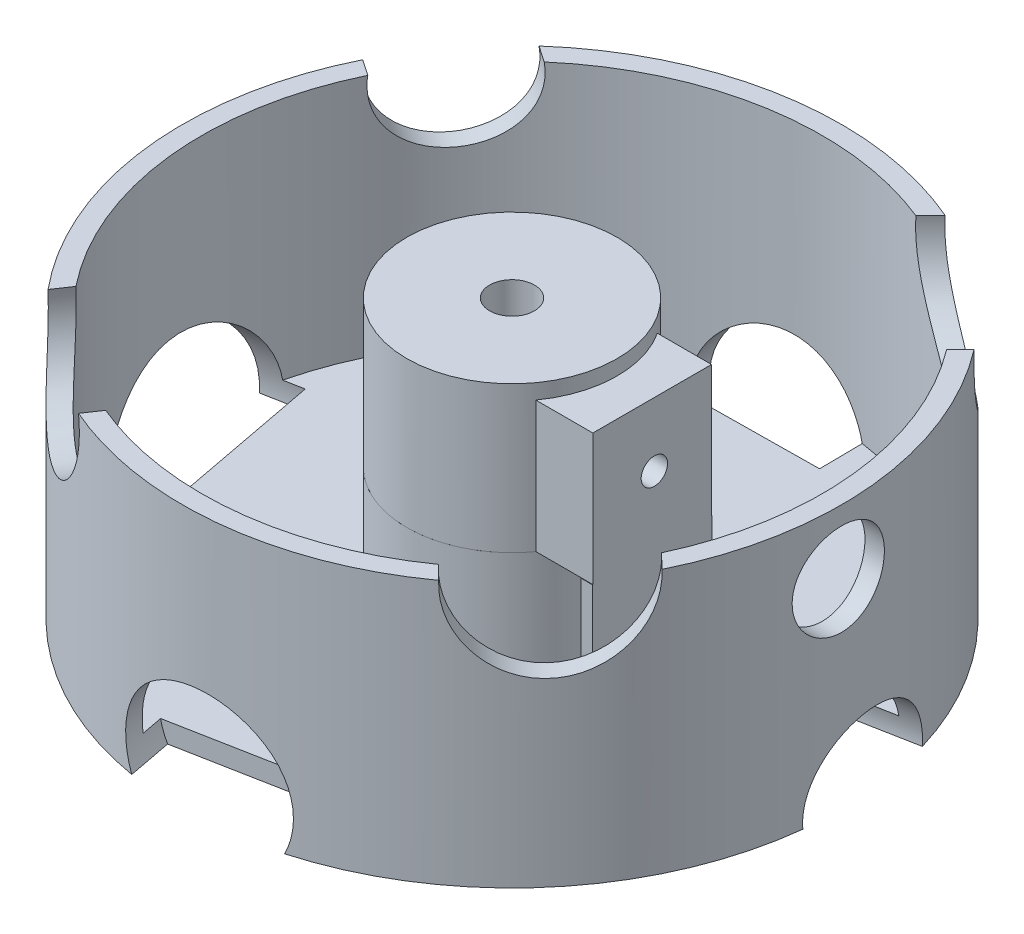
SolidWorks part; units mm, degrees
ref_plane "Front Plane" through (0, 0, 0) normal (0, 0, 1) x (1, 0, 0)
ref_plane "Top Plane" through (0, 0, 0) normal (0, 1, 0) x (1, 0, 0)
ref_plane "Right Plane" through (0, 0, 0) normal (1, 0, 0) x (0, 0, -1)
sketch "Sketch1" plane through (0, 0, 0) normal (0, 1, 0) x (1, 0, 0)
  circle A0 centre (0, 0) radius 15.958
extrude "ShaftHolderNearMotor" add sketch "Sketch1" along normal blind 22.19
sketch "Sketch2" plane through (0, 22.19, 0) normal (0, 1, 0) x (1, 0, 0)
  circle A0 centre (0, 0) radius 3.4
extrude "Cut-Extrude1" cut sketch "Sketch2" against normal blind 14.35 contours A0
ref_plane "Plane1" through (0, 19.65, 0) normal (0, 1, 0) x (1, 0, 0)
ref_axis "Axis1" through (0, 7.84, 0) along (0, 1, 0)
ref_point "Point2"
sketch "Sketch5" plane through (0, 19.65, 0) normal (0, 1, 0) x (1, 0, 0)
  line L0 (0, 0) -> (2.6, 0) construction
  line L2 (2.6, -3.5716) -> (4.1507, -3.5716)
  line L3 (2.6, -3.5716) -> (2.6, 3.6126)
  line L4 (2.6, 3.6126) -> (4.1507, 3.6126)
  line L5 (4.1507, -3.5716) -> (4.1507, 3.6126)
extrude "Boss-Extrude2" add sketch "Sketch5" against normal blind 13.55
sketch "Sketch7" plane through (2.6, 0, 0) normal (-1, 0, 0) x (0, 0, 1)
  line L1 (-8.6717, 19.91) -> (9.3323, 19.91)
  line L2 (-8.6717, 19.91) -> (-8.6717, 0)
  line L3 (-8.6717, 0) -> (9.3323, 0)
  line L4 (9.3323, 19.91) -> (9.3323, 0)
extrude "Boss-Extrude3" add sketch "Sketch7" against normal blind 19
sketch "Sketch6" plane through (2.6, 0, 0) normal (-1, 0, 0) x (0, 0, 1)
  line L1 (-2.1909, 7.84) -> (-2.1909, 19.91) construction
  line L2 (2.1909, 19.91) -> (2.1909, 7.84) construction
  line L3 (-2.1909, 15.4522) -> (2.1909, 15.4522) construction
  circle A0 centre (0, 10.2369) radius 2
extrude "Cut-Extrude2" cut sketch "Sketch6" against normal up to surface (19 mm away) and the other way blind 1 up to face at (21.6, 9.955, 0.3303)
ref_axis "Axis2" through (-1.8994, 10.2369, 0) along (-1, 0, 0)
ref_axis "Axis4" through (21.6, 10.2369, 0) along (-1, 0, 0)
ref_plane "Plane3" through (0, 0, 0) normal (0, 0, 1) x (1, 0, 0)
sketch "Sketch9" plane through (0, 0, 0) normal (0, 0, 1) x (1, 0, 0)
  line L0 (11.8765, 10.2369) -> (11.8765, 5.8619) construction
  line L1 (4.9434, 5.8619) -> (11.8765, 5.8619) construction
  line L2 (4.9434, 5.8619) -> (4.9434, 10.2369) construction
  line L3 (4.9434, 10.2369) -> (4.9434, 14.6143) construction
  line L4 (4.9434, 14.6143) -> (11.8765, 14.6143) construction
  line L5 (11.8765, 14.6143) -> (11.8765, 10.2369) construction
  line L6 (21.6, 10.2369) -> (2.6, 10.2369) construction
  line L7 (4.9434, 14.6143) -> (11.8765, 5.8619) construction
  line L8 (4.9434, 14.6143) -> (2.3367, 17.9051) construction
  line L9 (11.8765, 5.8619) -> (13.8203, 3.408) construction
  line L11 (4.652, 14.9822) -> (12.172, 14.9822)
  line L12 (4.652, 14.9822) -> (4.652, 5.4889)
  line L13 (4.652, 5.4889) -> (12.172, 5.4889)
  line L14 (12.172, 14.9822) -> (12.172, 5.4889)
  circle A0 centre (4.9434, 14.6143) radius 0.4693 construction
  circle A1 centre (11.8765, 5.8619) radius 0.4759 construction
extrude "NutOpening" cut sketch "Sketch9" against normal blind 30
sketch "Sketch10" plane through (0, 0, 0) normal (0, -1, 0) x (1, 0, 0)
  circle A0 centre (0, 0) radius 50
extrude "Boss-Extrude4" add sketch "Sketch10" along normal blind 20
sketch "Sketch11" plane through (0, 0, 0) normal (0, 1, 0) x (1, 0, 0)
  line L1 (31.7817, 38.8528) -> (14.4942, 48.0577) construction
  line L2 (14.4942, 48.0577) -> (-5, 49.9462) construction
  line L3 (-5, 49.9462) -> (-23.733, 44.2308) construction
  line L4 (-23.733, 44.2308) -> (-38.8528, 31.7817) construction
  line L5 (-38.8528, 31.7817) -> (-48.0577, 14.4942) construction
  line L6 (-48.0577, 14.4942) -> (-49.9462, -5) construction
  line L7 (-49.9462, -5) -> (-44.2308, -23.733) construction
  line L8 (-44.2308, -23.733) -> (-31.7817, -38.8528) construction
  line L9 (-31.7817, -38.8528) -> (-14.4942, -48.0577) construction
  line L10 (-14.4942, -48.0577) -> (5, -49.9462) construction
  line L11 (5, -49.9462) -> (23.733, -44.2308) construction
  line L12 (23.733, -44.2308) -> (38.8528, -31.7817) construction
  line L13 (38.8528, -31.7817) -> (48.0577, -14.4942) construction
  line L14 (48.0577, -14.4942) -> (49.9462, 5) construction
  line L15 (49.9462, 5) -> (44.2308, 23.733) construction
  line L16 (44.2308, 23.733) -> (31.7817, 38.8528) construction
  circle A0 centre (0, 0) radius 49.2313 construction
  circle A1 centre (5, -49.9462) radius 5
  circle A2 centre (-14.4942, -48.0577) radius 5
  circle A3 centre (-31.7817, -38.8528) radius 5
  circle A4 centre (-44.2308, -23.733) radius 5
  circle A5 centre (-49.9462, -5) radius 5
  circle A6 centre (-48.0577, 14.4942) radius 5
  circle A7 centre (-38.8528, 31.7817) radius 5
  circle A8 centre (-23.733, 44.2308) radius 5
  circle A9 centre (-5, 49.9462) radius 5
  circle A10 centre (14.4942, 48.0577) radius 5
  circle A11 centre (31.7817, 38.8528) radius 5
  circle A12 centre (44.2308, 23.733) radius 5
  circle A13 centre (49.9462, 5) radius 5
  circle A14 centre (48.0577, -14.4942) radius 5
  circle A15 centre (38.8528, -31.7817) radius 5
  circle A16 centre (23.733, -44.2308) radius 5
sketch "Sketch12" plane through (0, 0, 0) normal (0, 1, 0) x (1, 0, 0)
  circle A0 centre (0, 0) radius 47.0828
  circle A1 centre (0, 0) radius 15.9579
extrude "CutToRemveExcessMaterial" cut sketch "Sketch12" against normal offset from surface (17 mm away) 3 up to face at (0, -20, -50)
sketch "Sketch13" plane through (0, 0, 0) normal (0, 1, 0) x (1, 0, 0)
  circle A0 centre (0, 0) radius 47.0828
  circle A1 centre (0, 0) radius 50
extrude "Boss-Extrude5" add sketch "Sketch13" along normal blind 20
sketch "Sketch14" plane through (12.172, 0, 0) normal (-1, 0, 0) x (0, 0, 1)
  line L1 (-5.9541, 10.2369) -> (-2.9771, 5.0805)
  line L2 (-2.9771, 5.0805) -> (2.9771, 5.0805)
  line L3 (2.9771, 5.0805) -> (5.9541, 10.2369)
  line L4 (5.9541, 10.2369) -> (2.9771, 15.3933)
  line L5 (2.9771, 15.3933) -> (-2.9771, 15.3933)
  line L6 (-2.9771, 15.3933) -> (-5.9541, 10.2369)
  circle A0 centre (0, 10.2369) radius 5.1564 construction
extrude "Cut-Extrude6" cut sketch "Sketch14" along normal up to surface (7.52 mm away) up to face at (4.652, 10.236, -5.4216)
sketch "Sketch16" plane through (21.6, 0, 0) normal (1, 0, 0) x (0, 0, -1)
  circle A0 centre (0, 10.2369) radius 7
extrude "Cut-Extrude7" cut sketch "Sketch16" along normal blind 40
ref_plane "Plane4" through (-0.571, 0, -49.9967) normal (-0.0114, 0, -0.9999) x (-0.9999, 0, 0.0114)
ref_plane "Plane5" through (-27.4359, 0, -41.8004) normal (-0.5487, 0, -0.836) x (-0.836, 0, 0.5487)
sketch "Sketch17" plane through (-0.571, 0, -49.9967) normal (-0.0114, 0, -0.9999) x (-0.9999, 0, 0.0114)
  line L1 (-6.9779, 26.3682) -> (19.0025, 26.3682)
sketch "Sketch18" plane through (-27.4359, 0, -41.8004) normal (-0.5487, 0, -0.836) x (-0.836, 0, 0.5487)
  line L1 (2.3429, -8.8145) -> (-7.3736, -8.8145)
  line L2 (2.3429, -8.8145) -> (2.3429, -36.514)
  line L3 (2.3429, -36.514) -> (-7.3736, -36.514)
  line L4 (-7.3736, -8.8145) -> (-7.3736, -36.514)
ref_plane "Plane6" through (18.6054, 0, -46.4095) normal (0.3721, 0, -0.9282) x (-0.9282, 0, -0.3721)
ref_plane "Plane7" through (34.9493, 0, -35.7568) normal (0.699, 0, -0.7151) x (-0.7151, 0, -0.699)
ref_plane "Plane8" through (45.9725, 0, -19.6605) normal (0.9194, 0, -0.3932) x (-0.3932, 0, -0.9194)
ref_plane "Plane9" through (49.1178, 0, -9.3511) normal (0.9824, 0, -0.187) x (-0.187, 0, -0.9824)
ref_plane "Plane10" through (46.4095, 0, 18.6054) normal (0.9282, 0, 0.3721) x (0.3721, 0, -0.9282)
ref_plane "Plane11" through (35.7568, 0, 34.9493) normal (0.7151, 0, 0.699) x (0.699, 0, -0.7151)
ref_plane "Plane12" through (9.3511, 0, 49.1178) normal (0.187, 0, 0.9824) x (0.9824, 0, -0.187)
ref_plane "Plane13" through (-28.1193, 0, 41.3438) normal (-0.5624, 0, 0.8269) x (0.8269, 0, 0.5624)
ref_plane "Plane14" through (-49.1178, 0, 9.3511) normal (-0.9824, 0, 0.187) x (0.187, 0, 0.9824)
ref_plane "Plane15" through (-41.3438, 0, -28.1193) normal (-0.8269, 0, -0.5624) x (-0.5624, 0, 0.8269)
sketch "Sketch19" plane through (9.3511, 0, 49.1178) normal (0.187, 0, 0.9824) x (0.9824, 0, -0.187)
  circle A0 centre (-6.5538, -15.0444) radius 12
extrude "Cut-Extrude8" cut sketch "Sketch19" against normal blind 10
sketch "Sketch20" plane through (35.7568, 0, 34.9493) normal (0.7151, 0, 0.699) x (0.699, 0, -0.7151)
  circle A0 centre (3.5584, 19.4292) radius 12
extrude "Cut-Extrude9" cut sketch "Sketch20" against normal blind 10
sketch "Sketch21" plane through (49.1178, 0, -9.3511) normal (0.9824, 0, -0.187) x (-0.187, 0, -0.9824)
  circle A0 centre (-4.7912, -19.2219) radius 10
sketch "Sketch22" plane through (34.9493, 0, -35.7568) normal (0.699, 0, -0.7151) x (-0.7151, 0, -0.699)
  circle A0 centre (5.4277, 18.4908) radius 12.5535
extrude "Cut-Extrude10" cut sketch "Sketch22" against normal blind 10
extrude "Cut-Extrude11" cut sketch "Sketch21" against normal blind 10 contours A0
sketch "Sketch23" plane through (-0.571, 0, -49.9967) normal (-0.0114, 0, -0.9999) x (-0.9999, 0, 0.0114)
  circle A0 centre (4.5252, -20.0178) radius 11.9653
extrude "Cut-Extrude12" cut sketch "Sketch23" against normal blind 10
sketch "Sketch25" plane through (-41.3438, 0, -28.1193) normal (-0.8269, 0, -0.5624) x (-0.5624, 0, 0.8269)
  circle A0 centre (-2.6498, 18.6432) radius 9.6297
extrude "Cut-Extrude13" cut sketch "Sketch25" against normal blind 10
sketch "Sketch26" plane through (-49.1178, 0, 9.3511) normal (-0.9824, 0, 0.187) x (0.187, 0, 0.9824)
  circle A0 centre (-4.4977, -19.1264) radius 15.0124
extrude "Cut-Extrude14" cut sketch "Sketch26" against normal blind 10
sketch "Sketch27" plane through (-28.1193, 0, 41.3438) normal (-0.5624, 0, 0.8269) x (0.8269, 0, 0.5624)
  circle A0 centre (-2.2875, 17.6222) radius 11.8547
extrude "Cut-Extrude15" cut sketch "Sketch27" against normal blind 10
sketch "Sketch28" plane through (0, 0, 0) normal (0, -1, 0) x (1, 0, 0)
  line L1 (19.8832, 9.4042) -> (21.6, 9.4042)
  line L2 (19.8832, 9.4042) -> (19.8832, -8.7683)
  line L3 (19.8832, -8.7683) -> (21.6, -8.7683)
  line L4 (21.6, 9.4042) -> (21.6, -8.7683)
extrude "Boss-Extrude6" add sketch "Sketch28" along normal up to surface (17 mm away) up to face at (-0.493, -17, 0.1034)
